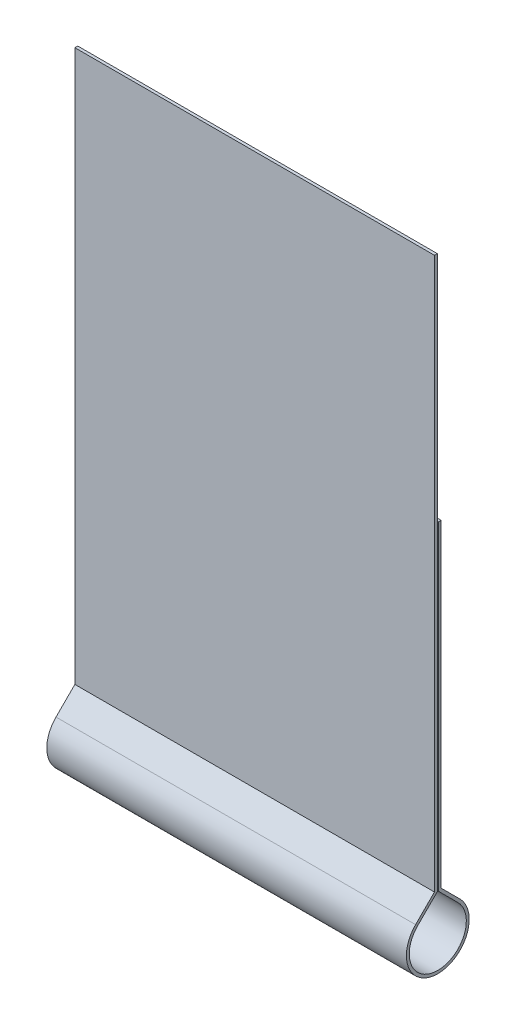
SolidWorks part; units mm, degrees
material "AISI 1045 Steel, cold drawn"
ref_plane "Front" through (0, 0, 0) normal (0, 0, 1) x (1, 0, 0)
ref_plane "Top" through (0, 0, 0) normal (0, 1, 0) x (1, 0, 0)
ref_plane "Right" through (0, 0, 0) normal (1, 0, 0) x (0, 0, -1)
ref_axis "side-side" through (80.9, 0, 0) along (-1, 0, 0)
ref_axis "up-down" through (0, 50, 0) along (0, -1, 0)
ref_axis "front-back" through (0, 0, -80.9) along (0, 0, 1)
sketch "Sketch1" plane through (0, 0, 0) normal (1, 0, 0) x (0, 0, -1)
  line L0 (0.1016, 2.1435) -> (0.1016, 19.05)
  line L1 (0, 50) -> (0, -50) construction
  line L2 (-0.1016, 2.1435) -> (-0.1016, 31.39)
  line L3 (1.1225, 1.1225) -> (0.1016, 2.1435)
  line L4 (0, 0) -> (0, 1.8624) construction
  line L5 (-1.1225, 1.1225) -> (-0.1016, 2.1435)
  arc A0 (-1.1225, 1.1225) -> (1.1225, 1.1225) centre (0, 0) ccw
  dimension "D1" = 3.175
  dimension "D2" = 0.1016
  dimension "D3" = 0.1016
  dimension "D4" = 45
  dimension "D5" = 31.39
  dimension "D6" = 19.05
extrude "Extrude-Thin1" add sketch "Sketch1" along normal mid plane 19.05 thin thin type mid plane wall 0.1524
